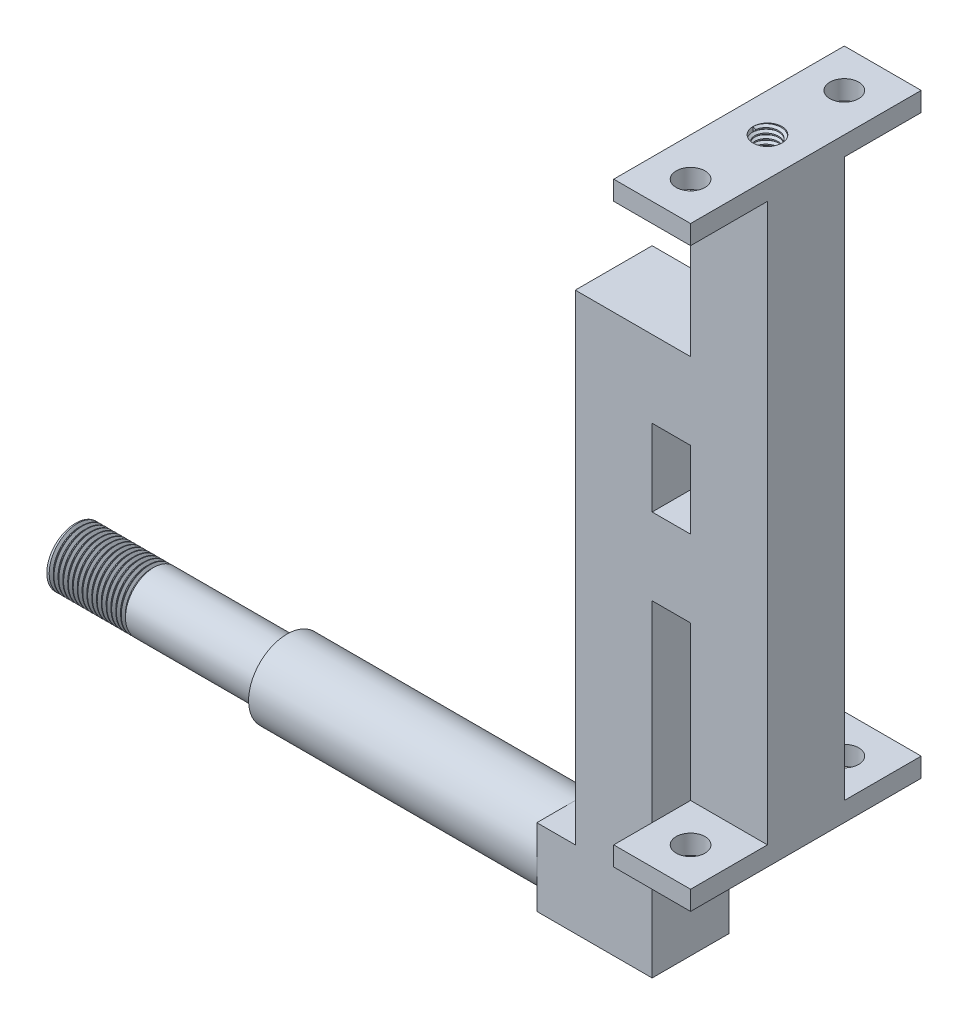
SolidWorks part; units mm, degrees
material "Plain Carbon Steel"
ref_plane "Front Plane" through (0, 0, 0) normal (0, 0, 1) x (1, 0, 0)
ref_plane "Top Plane" through (0, 0, 0) normal (0, 1, 0) x (1, 0, 0)
ref_plane "Right Plane" through (0, 0, 0) normal (1, 0, 0) x (0, 0, -1)
sketch "Sketch1" plane through (0, 0, 0) normal (0, 1, 0) x (1, 0, 0)
  line L1 (12.7, -12.7) -> (-12.7, -12.7)
  line L2 (12.7, -12.7) -> (12.7, 12.7)
  line L3 (12.7, 12.7) -> (-12.7, 12.7)
  line L4 (-12.7, -12.7) -> (-12.7, 12.7)
  line L5 (12.7, -12.7) -> (-12.7, 12.7) construction
  line L6 (12.7, 12.7) -> (-12.7, -12.7) construction
  line L7 (10.16, -10.16) -> (-10.16, -10.16)
  line L8 (10.16, -10.16) -> (10.16, 10.16)
  line L9 (10.16, 10.16) -> (-10.16, 10.16)
  line L10 (-10.16, -10.16) -> (-10.16, 10.16)
  line L11 (10.16, -10.16) -> (-10.16, 10.16) construction
  line L12 (10.16, 10.16) -> (-10.16, -10.16) construction
  point P0 (0, 0)
  point P5 (0, 0)
  dimension "D1" = 2.54
  dimension "1" = 25.4
extrude "Sq_Tb Extrude" add sketch "Sketch1" along normal blind 196.85
sketch "Sketch3" plane through (0, 196.85, 0) normal (0, 1, 0) x (1, 0, 0)
  line L0 (12.7, -12.7) -> (12.7, 12.7) construction
  line L1 (10.16, -10.16) -> (-10.16, -10.16)
  line L2 (10.16, -10.16) -> (10.16, 10.16)
  line L3 (10.16, 10.16) -> (-10.16, 10.16)
  line L4 (-10.16, -10.16) -> (-10.16, 10.16)
  line L5 (10.16, -10.16) -> (-10.16, 10.16) construction
  line L6 (10.16, 10.16) -> (-10.16, -10.16) construction
  line L7 (-12.7, 12.7) -> (12.7, 12.7)
  line L8 (-12.7, 12.7) -> (-12.7, 38.1)
  line L9 (-12.7, 38.1) -> (12.7, 38.1)
  line L10 (12.7, 12.7) -> (12.7, 38.1)
  line L11 (-12.7, 12.7) -> (12.7, 38.1) construction
  line L12 (-12.7, 38.1) -> (12.7, 12.7) construction
  line L13 (0, 0) -> (12.7, 0) construction
  line L14 (-12.7, -38.1) -> (12.7, -12.7) construction
  line L15 (-12.7, -12.7) -> (12.7, -38.1) construction
  line L16 (12.7, -12.7) -> (12.7, -38.1)
  line L17 (-12.7, -38.1) -> (12.7, -38.1)
  line L18 (-12.7, -12.7) -> (-12.7, -38.1)
  line L19 (-12.7, -12.7) -> (12.7, -12.7)
  circle A0 centre (0, 0) radius 4.7625
  circle A1 centre (0, 25.4) radius 4.7625
  circle A2 centre (0, -25.4) radius 4.7625
  point P0 (0, 0)
  point P13 (0, 25.4)
  point P26 (0, -25.4)
  dimension "D1" = 9.525
  dimension "D3" = 50.8
  dimension "D2" = 25.4
extrude "End Caps" add sketch "Sketch3" against normal blind 6.35
ref_plane "Mid-Plane" through (0, 98.425, 0) normal (0, 1, 0) x (1, 0, 0)
mirror "End Cap Mirror" about plane through (0, 98.425, 0) normal (0, 1, 0) of "End Caps"
thread "Top Thread" pitch 1.5875 method extrude profile "Thread Profile1" start angle 0, offset 0, length 0, pitch 1.5875, diameter 9.525
ref_plane "Plane2" through (-4.7625, 196.85, 0) normal (0, 0, 1) x (-1, 0, 0)
sketch "Thread Profile1" plane through (-4.7625, 196.85, 0) normal (0, 0, 1) x (-1, 0, 0)
  line L0 (0, 0) -> (0, 1.5875) construction
  line L11 (0, 0) -> (0, 1.3891)
  line L12 (0, 1.3891) -> (-0.8593, 0.893)
  line L13 (-0.8593, 0.893) -> (-0.8593, 0.4961)
  line L15 (-0.8593, 0.4961) -> (0, 0)
  line L17 (-0.8593, 0.6945) -> (0, 0.6945) construction
  point P2 (0, 0)
  dimension "Pitch" = 1.5875
  dimension "Profile_Angle" = 60
  dimension "Profile_Land" = 0.3969
  dimension "Profile_Height" = 0.8593
thread "Bottom Thread" pitch 1.5875 method extrude profile "Thread Profile2" start angle 0, offset 0, length 0, pitch 1.5875, diameter 9.525
ref_plane "Plane3" through (4.7625, 0, 0) normal (0, 0, 1) x (1, 0, 0)
sketch "Thread Profile2" plane through (4.7625, 0, 0) normal (0, 0, 1) x (1, 0, 0)
  line L0 (0, 0) -> (0, 1.5875) construction
  line L11 (0, 0) -> (0, 1.3891)
  line L12 (0, 1.3891) -> (-0.8593, 0.893)
  line L13 (-0.8593, 0.893) -> (-0.8593, 0.4961)
  line L15 (-0.8593, 0.4961) -> (0, 0)
  line L17 (-0.8593, 0.6945) -> (0, 0.6945) construction
  point P2 (0, 0)
  dimension "Pitch" = 1.5875
  dimension "Profile_Angle" = 60
  dimension "Profile_Land" = 0.3969
  dimension "Profile_Height" = 0.8593
sketch "Sketch9" plane through (0, 0, 0) normal (0, 0, 1) x (1, 0, 0)
  line L1 (-12.7, 190.5) -> (-12.7, 6.35) construction
  line L11 (-25.4, -50.8) -> (-63.5, -50.8)
  line L12 (-63.5, -50.8) -> (-63.5, -25.4)
  line L13 (-63.5, -25.4) -> (-63.1415, -25.4)
  line L15 (-63.5, -38.1) -> (0, -38.1) construction
  line L16 (0, -38.1) -> (0, 0) construction
  line L24 (-25.4, -25.4) -> (-25.4, -50.8)
  line L27 (-25.4, 107.95) -> (-50.8, 107.95) construction
  line L28 (-50.8, 107.95) -> (-50.8, -25.4)
  line L29 (-50.8, 107.95) -> (-50.8, 133.35)
  line L30 (-50.8, 133.35) -> (-12.7, 133.35)
  line L31 (-12.7, 190.5) -> (-12.7, 6.35) construction
  line L32 (-25.4, 107.95) -> (-12.7, 107.95)
  line L33 (-25.4, 57.15) -> (-12.7, 57.15)
  line L34 (-25.4, 82.55) -> (-12.7, 82.55)
  line L35 (-19.05, 82.55) -> (-19.05, 57.15) construction
  line L36 (-25.4, 107.95) -> (-50.8, 133.35) construction
  line L37 (-63.1415, -25.4) -> (-50.8, -25.4)
  line L38 (-50.8, -25.4) -> (-25.4, -25.4) construction
  line L39 (-50.8, -25.4) -> (-25.4, -50.8) construction
  line L40 (-12.7, 133.35) -> (-12.7, 107.95)
  line L41 (12.7, 190.5) -> (-12.7, 190.5) construction
  line L42 (-12.7, 0) -> (12.7, 0) construction
  line L43 (-25.4, 107.95) -> (-25.4, 82.55)
  line L44 (-25.4, 57.15) -> (-25.4, -25.4)
  line L45 (-12.7, 82.55) -> (-12.7, 57.15)
  dimension "D1" = 25.4
  dimension "D2" = 50.8
  dimension "D3" = 25.4
  dimension "D4" = 57.15
  dimension "D5" = 57.15
  dimension "D6" = 50.8
  dimension "D8" = 38.1
extrude "Sq_Tb Angles" add sketch "Sketch9" along normal blind 12.7 and the other way blind 12.7 contours L13 L12 L11 region at (-37.0114, 42.9079, 0)
sketch "Sketch11" plane through (0, 0, 0) normal (0, 0, 1) x (1, 0, 0)
  line L0 (-63.5, -38.1) -> (-228.6, -38.1)
  line L1 (-63.5, -50.8) -> (-63.5, -25.4) construction
  line L2 (-228.6, -38.1) -> (-228.6, -28.575)
  line L3 (-228.6, -28.575) -> (-158.75, -28.575)
  line L4 (-158.75, -28.575) -> (-158.75, -25.4)
  line L5 (-158.75, -25.4) -> (-63.5, -25.4)
  line L6 (-63.5, -25.4) -> (-63.5, -38.1)
  dimension "D1" = 12.7
  dimension "D2" = 9.525
  dimension "D3" = 95.25
  dimension "D4" = 69.85
revolve "Wheel Rod" add sketch "Sketch11" angle 360 about L0
thread "Wheel Threads" pitch 1.5875 method cut profile "Thread Profile3" start angle 0, offset 0, length 25.4, pitch 1.5875, diameter 19.05
ref_plane "Plane4" through (-228.6, -38.1, -9.525) normal (0, -1, 0) x (0, 0, -1)
sketch "Thread Profile3" plane through (-228.6, -38.1, -9.525) normal (0, -1, 0) x (0, 0, -1)
  line L0 (0, 0) -> (0, 1.5875) construction
  line L11 (0, 0) -> (0, 1.3891)
  line L12 (0, 1.3891) -> (-0.8593, 0.893)
  line L13 (-0.8593, 0.893) -> (-0.8593, 0.4961)
  line L15 (-0.8593, 0.4961) -> (0, 0)
  line L17 (-0.8593, 0.6945) -> (0, 0.6945) construction
  point P2 (0, 0)
  dimension "Pitch" = 1.5875
  dimension "Profile_Angle" = 60
  dimension "Profile_Land" = 0.3969
  dimension "Profile_Height" = 0.8593
ref_plane "Tie-Rod Mount Plane" through (0, 44.45, 0) normal (0, 1, 0) x (1, 0, 0)
sketch "Sketch12" plane through (-50.8, 0, 0) normal (-1, 0, 0) x (0, 0, 1)
  line L0 (70.3677, -15.3502) -> (82.8271, -27.8097)
  line L1 (82.8271, -27.8097) -> (55.8864, -54.7505)
  line L2 (55.8864, -54.7505) -> (-6.9754, 8.1113)
  line L3 (24.4555, -23.3196) -> (36.2877, -11.4874) construction
  line L4 (19.9653, 35.0521) -> (-6.9754, 8.1113)
  line L5 (32.4248, 22.5926) -> (19.9653, 35.0521)
  line L6 (32.4248, 22.5926) -> (70.3677, -15.3502)
  line L7 (22.3872, 19.1599) -> (66.9349, -25.3879) construction
  line L8 (24.4555, -23.3196) -> (44.661, -3.114) construction
  line L9 (52.9971, 5.2221) -> (51.3962, 3.6212) construction
  line L11 (12.7, -25.4) -> (12.7, 133.35) construction
  circle A0 centre (66.9349, -25.3879) radius 3.175
  circle A1 centre (22.3872, 19.1599) radius 3.175
  arc A2 (70.3677, -15.3502) -> (32.4248, 22.5926) centre (52.9971, 5.2221) cw
  circle A3 centre (0, -38.1) radius 28.575 construction
  point P11 (66.9349, -25.3879)
  line M12 (12.7, -25.4) -> (12.7, 133.35)
  dimension "D2" = 6.35
  dimension "D3" = 26.925
  dimension "D9" = 57.15
  dimension "D1" = 63
  dimension "D4" = 38.1
  dimension "D5" = 88.9
  dimension "D6" = 16.7333
  dimension "D7" = 28.575
  dimension "D8" = 2.264
  dimension "D10" = 135
extrude "Boss-Extrude1" [suppressed] add sketch "Sketch12" along normal blind 6.35 contours L0 A2 L5 L4 L2 L1 A1 A0 M12 | L4 L2 M12
